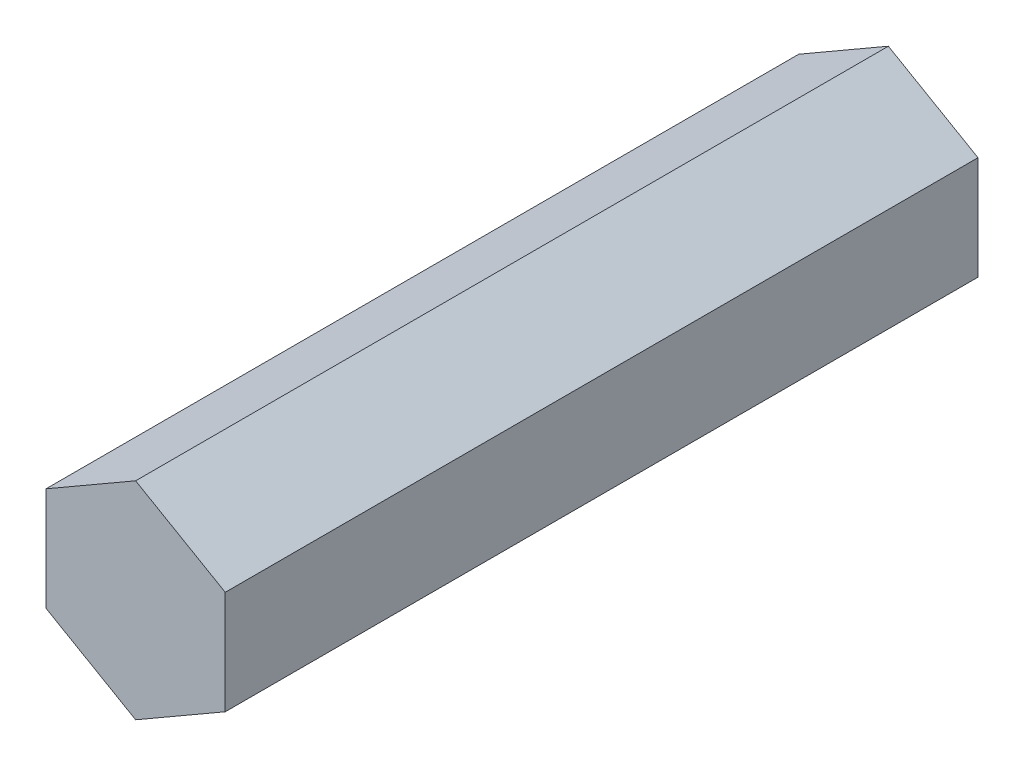
SolidWorks part; units mm, degrees
ref_plane "Front Plane" through (0, 0, 0) normal (0, 0, 1) x (1, 0, 0)
ref_plane "Top Plane" through (0, 0, 0) normal (0, 1, 0) x (1, 0, 0)
ref_plane "Right Plane" through (0, 0, 0) normal (1, 0, 0) x (0, 0, -1)
sketch "Sketch1" plane through (0, 0, 0) normal (0, 0, 1) x (1, 0, 0)
  line L1 (4.7625, 2.7496) -> (0, 5.4993)
  line L2 (0, 5.4993) -> (-4.7625, 2.7496)
  line L3 (-4.7625, 2.7496) -> (-4.7625, -2.7496)
  line L4 (-4.7625, -2.7496) -> (0, -5.4993)
  line L5 (0, -5.4993) -> (4.7625, -2.7496)
  line L6 (4.7625, -2.7496) -> (4.7625, 2.7496)
  circle A0 centre (0, 0) radius 4.7625 construction
  point P11 (0, 0)
  dimension "D1" = 9.525
extrude "Boss-Extrude1" add sketch "Sketch1" along normal mid plane 40
ref_axis "Axis2" through (0, 0, 0) along (0, 0, 1)
